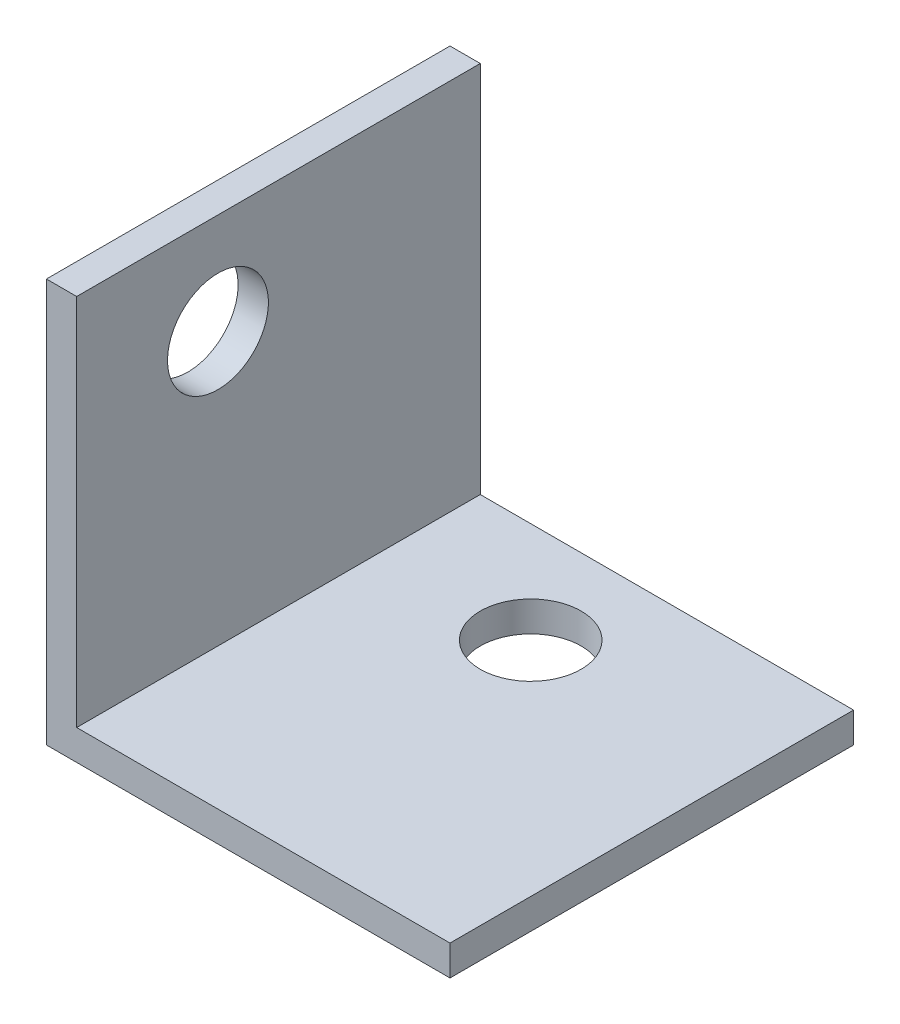
SolidWorks part; units mm, degrees
material "1060 Alloy"
ref_plane "xy" through (0, 0, 0) normal (0, 0, 1) x (1, 0, 0)
ref_plane "xz" through (0, 0, 0) normal (0, 1, 0) x (1, 0, 0)
ref_plane "yz" through (0, 0, 0) normal (1, 0, 0) x (0, 0, -1)
ref_axis "x" through (-1, 0, 0) along (1, 0, 0)
ref_axis "y" through (0, 21, 0) along (0, -1, 0)
ref_axis "z" through (0, 0, -2.575) along (0, 0, 1)
sketch "Sketch1" plane through (0, 0, 0) normal (0, 0, 1) x (1, 0, 0)
  line L0 (0, 0) -> (20, 0)
  line L1 (0, 0) -> (0, 20)
  dimension "D1" = 20
extrude "Extrude-Thin1" add sketch "Sketch1" along normal blind 20 thin thin type one direction wall 1.5
sketch "Sketch2" plane through (0, 0, 0) normal (0, -1, 0) x (-1, 0, 0)
  line L0 (-9, 0) -> (-9, -15) construction
  line L2 (-20, -20) -> (-20, 0) construction
  line L3 (-20, 0) -> (-1.5, 0) construction
  circle A0 centre (-9, -15) radius 2.5
  dimension "D2" = 5
  dimension "D1" = 15
  dimension "D3" = 11
extrude "Cut-Extrude1" cut sketch "Sketch2" against normal through all
sketch "Sketch3" plane through (1.5, 0, 0) normal (1, 0, 0) x (0, 0, -1)
  line L0 (-7, 15) -> (-7, 20) construction
  line L1 (-20, 20) -> (0, 20) construction
  line L2 (0, 1.5) -> (0, 20) construction
  circle A0 centre (-7, 15) radius 2.5
  dimension "D1" = 5
  dimension "D2" = 5
  dimension "D3" = 7
extrude "Cut-Extrude2" cut sketch "Sketch3" against normal through all
mirror "Mirror1" about plane through (0, 0, 0) normal (0, 0, 1) of bodies 103
delete or keep bodies "Body-Delete/Keep 1" type delete bodies bodies 103
